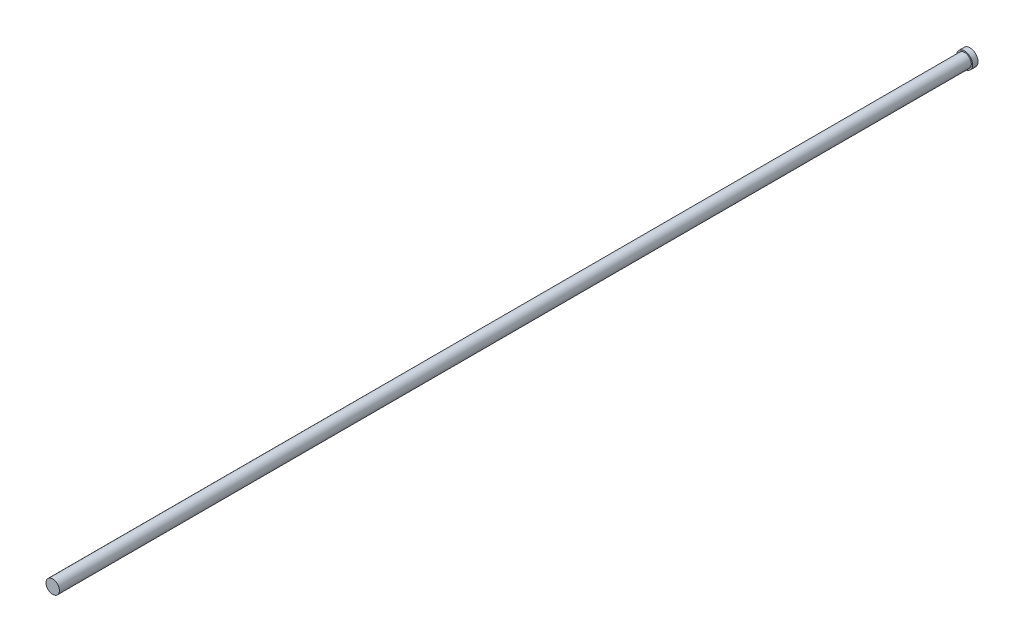
SolidWorks part; units mm, degrees
ref_plane "Front Plane" through (0, 0, 0) normal (0, 0, 1) x (1, 0, 0)
ref_plane "Top Plane" through (0, 0, 0) normal (0, 1, 0) x (1, 0, 0)
ref_plane "Right Plane" through (0, 0, 0) normal (1, 0, 0) x (0, 0, -1)
sketch "Sketch2" plane through (0, 0, 0) normal (0, 0, 1) x (1, 0, 0)
  circle A0 centre (-13.0879, 5.5684) radius 3
  circle A1 centre (-13.0869, 5.5492) radius 2.5
  dimension "D1" = 6
  dimension "D2" = 5
extrude "Boss-Extrude1" add sketch "Sketch2" along normal blind 340 contours A1
extrude "Boss-Extrude2" add sketch "Sketch2<5>" against normal blind 2 contours A0
sketch "Sketch2<5>" plane through (0, 0, 0) normal (0, 0, 1) x (1, 0, 0) same geometry as "Sketch2"
